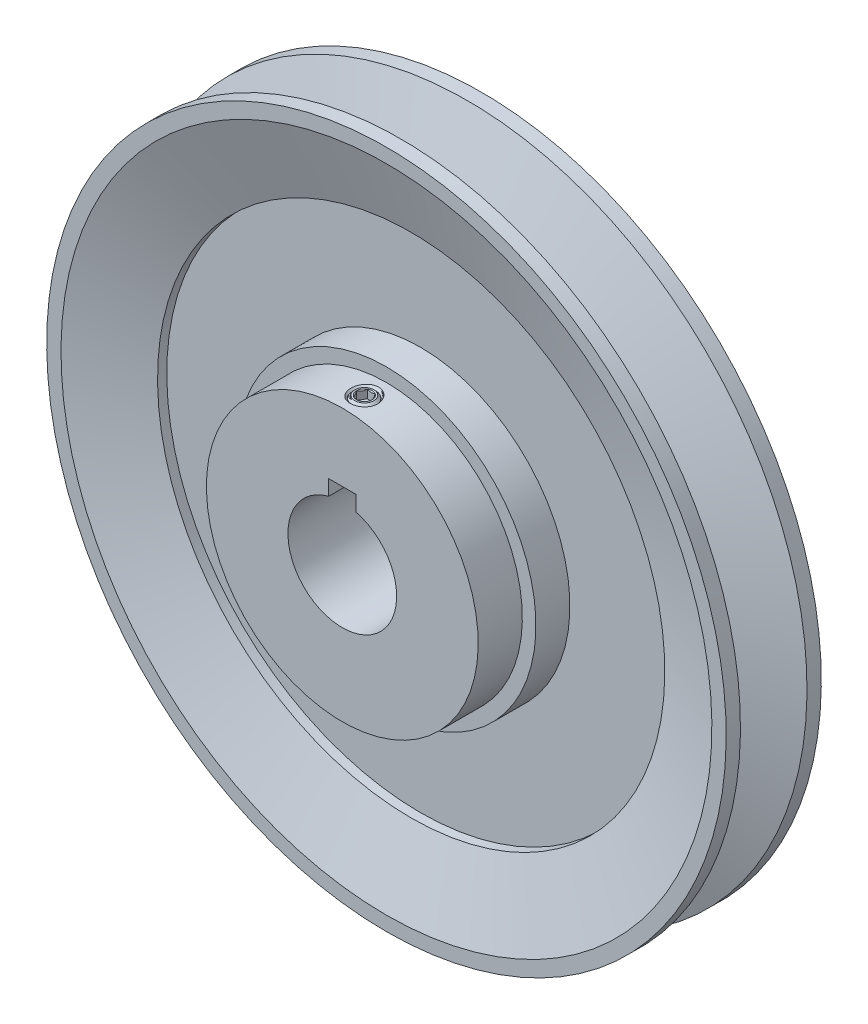
SolidWorks part; units mm, degrees
ref_plane "Front Plane" through (0, 0, 0) normal (0, 0, 1) x (1, 0, 0)
ref_plane "Top Plane" through (0, 0, 0) normal (0, 1, 0) x (1, 0, 0)
ref_plane "Right Plane" through (0, 0, 0) normal (1, 0, 0) x (0, 0, -1)
sketch "Sketch1" plane through (0, 0, 0) normal (1, 0, 0) x (0, 0, -1)
  line L0 (-21.4249, 0) -> (11.1125, 0) construction
  line L1 (-7.7724, 79.375) -> (7.7724, 79.375) construction
  line L2 (7.7724, 79.375) -> (11.1125, 79.375)
  line L5 (-11.1125, 79.375) -> (11.1125, 79.375) construction
  line L7 (-11.1125, 0) -> (-11.1125, 34.925)
  line L9 (-11.1125, 34.925) -> (-3.175, 34.925)
  line L13 (-7.7724, 79.375) -> (-2.3062, 63.5)
  line L14 (-2.3062, 63.5) -> (2.3062, 63.5)
  line L15 (2.3062, 63.5) -> (7.7724, 79.375)
  line L16 (7.9439, 12.7) -> (-21.4249, 12.7) construction
  line L17 (0, 79.375) -> (0, 0) construction
  line L18 (-7.7724, 79.375) -> (-11.1125, 79.375)
  line L20 (-21.4249, 0) -> (-21.4249, 12.7) construction
  line L22 (4.4927, 69.85) -> (-4.4927, 69.85) construction
  line L23 (11.1125, 79.375) -> (11.1125, 0) construction
  line L24 (-3.175, 34.925) -> (-3.175, 59.2544)
  line L26 (-11.1125, 0) -> (7.9439, 0)
  line L27 (-5.3345, 59.2544) -> (-11.1125, 76.0349)
  line L28 (7.9439, 34.925) -> (3.175, 34.925)
  line L29 (3.175, 34.925) -> (3.175, 59.2544)
  line L31 (5.3345, 59.2544) -> (11.1125, 76.0349)
  line L32 (-11.1125, 76.0349) -> (-11.1125, 79.375)
  line L33 (11.1125, 76.0349) -> (11.1125, 79.375)
  line L34 (-21.4249, 31.75) -> (-21.4249, -31.75) construction
  line L35 (6.2419, 74.93) -> (-6.2419, 74.93) construction
  line L36 (-3.175, 59.2544) -> (3.175, 59.2544) construction
  line L37 (-3.175, 34.925) -> (3.175, 34.925) construction
  line L38 (-5.3345, 59.2544) -> (-3.175, 59.2544)
  line L39 (3.175, 59.2544) -> (5.3345, 59.2544)
  line L40 (-2.3062, 63.5) -> (-6.3205, 62.1178) construction
  line L41 (-2.3062, 63.5) -> (-2.3062, 59.2544) construction
  line L42 (7.9439, 34.925) -> (7.9439, 0)
  point P16 (0, 63.5)
  point P33 (0, 59.2544)
  point P34 (0, 34.925)
  point P38 (-11.1061, 0)
  dimension "D1" = 3.175
  dimension "D2" = 6.35
revolve "Revolve1" add sketch "Sketch1" angle 360 about L0
sketch "Sketch2" plane through (0, 0, 0) normal (1, 0, 0) x (0, 0, -1)
  line L0 (11.1125, 0) -> (-21.4249, 0) construction
  line L3 (-11.1061, 0) -> (-11.1061, 31.75)
  line L4 (-11.1061, 31.75) -> (-21.4249, 31.75)
  line L5 (-21.4249, 31.75) -> (-21.4249, 0)
  line L8 (-21.4249, 0) -> (-11.1061, 0)
revolve "Revolve2" add sketch "Sketch2" angle 360 about L0
sketch "Sketch3" plane through (0, 0, 21.4249) normal (0, 0, -1) x (-1, 0, 0)
  line L0 (-3.175, 12.7) -> (3.175, 12.7) construction
  line L1 (-3.175, 15.875) -> (3.175, 15.875) construction
  line L2 (-3.175, 15.875) -> (-3.175, 9.525) construction
  line L3 (-3.175, 9.525) -> (3.175, 9.525) construction
  line L4 (3.175, 15.875) -> (3.175, 9.525) construction
  circle A0 centre (0, 0) radius 12.7
  circle A1 centre (0, 0) radius 69.85 construction
  circle A2 centre (0, 0) radius 74.93 construction
  dimension "Keyway Wd." = 6.35
  dimension "Keyway Dp." = 3.175
extrude "Cut-Extrude1" cut sketch "Sketch3" along normal up to vertex (32.5374 mm away) up to point (0, 0, -11.1125)
sketch "Sketch4" plane through (0, 0, 21.4249) normal (0, 0, -1) x (-1, 0, 0)
  line L0 (-3.175, 15.875) -> (-3.175, 9.525) construction
  line L1 (-3.175, 15.875) -> (3.175, 15.875) construction
  line L2 (3.175, 15.875) -> (3.175, 9.525) construction
  line L3 (-3.175, 9.525) -> (3.175, 9.525) construction
  line L4 (-3.175, 15.875) -> (-3.175, 9.525)
  line L5 (-3.175, 15.875) -> (3.175, 15.875)
  line L6 (3.175, 15.875) -> (3.175, 9.525)
  line L7 (-3.175, 9.525) -> (3.175, 9.525)
  line L8 (-3.175, 12.7) -> (3.175, 12.7) construction
  line L9 (-3.175, 12.7) -> (3.175, 12.7) construction
extrude "Cut-Extrude2" cut sketch "Sketch4" along normal up to vertex (32.5374 mm away) up to point (0, 0, -11.1125)
ref_plane "Plane1" through (0, 31.75, 0) normal (0, 1, 0) x (-1, 0, 0)
sketch "Sketch5" plane through (0, 31.75, 0) normal (0, 1, 0) x (-1, 0, 0)
  line L0 (0, 11.1061) -> (0, 21.4249) construction
  line L7 (0, 19.4405) -> (0, 18.1705) construction
  circle A0 centre (0, 16.2655) radius 3.175 construction
  circle A1 centre (0, 16.2655) radius 2.3813
  dimension "D3" = 0.7937
extrude "Cut-Extrude3" cut sketch "Sketch5" against normal up to vertex (31.75 mm away) up to point (0, 0, 0)
sketch "Sketch6" plane through (0, 31.75, 0) normal (0, 1, 0) x (-1, 0, 0)
  circle A0 centre (0, 16.2655) radius 3.175 construction
  circle A1 centre (0, 16.2655) radius 3.175
  point P3 (0, 19.4405)
curve "Helix/Spiral1" pitch 1.27 height 33.02 turns 26
sketch "Sketch7" plane through (0, 0, 0) normal (1, 0, 0) x (0, 0, -1)
  line L0 (-18.4782, 33.02) -> (-18.4782, 31.75) construction
  line L1 (-18.4782, 31.75) -> (-19.578, 32.385) construction
  line L2 (-19.578, 32.385) -> (-18.4782, 33.02) construction
  line L3 (-18.4782, 31.75) -> (-19.4405, 31.75) construction
  line L4 (-19.4405, 31.75) -> (-19.4405, 32.3056) construction
  line L5 (-19.4405, 32.3056) -> (-19.4405, 32.4644) construction
  line L6 (-18.6156, 31.8294) -> (-18.6156, 32.9406) construction
  line L7 (-19.578, 32.385) -> (-19.4405, 32.385) construction
  line L8 (-18.6156, 32.385) -> (-18.4782, 32.385) construction
  line L9 (-18.5469, 32.9803) -> (-18.5469, 31.7897)
  line L10 (-18.5469, 31.7897) -> (-19.4405, 32.3056)
  line L11 (-19.4405, 32.3056) -> (-19.4405, 32.4644)
  line L12 (-19.4405, 32.4644) -> (-18.5469, 32.9803)
  point P16 (-18.5469, 32.385)
  dimension "D1" = 1.27
  dimension "D2" = 0.1588
sweep "Cut-Sweep1" cut profiles "Sketch7" path "Helix/Spiral1"
sketch "Sketch8" plane through (0, 31.75, 0) normal (0, 1, 0) x (-1, 0, 0)
  circle A0 centre (0, 16.2655) radius 3.3125
extrude "Cut-Extrude4" cut sketch "Sketch8" against normal through all draft 45
sketch "Sketch9" plane through (0, 0, 0) normal (1, 0, 0) x (0, 0, -1)
  line L0 (-16.2655, 31.75) -> (-16.2655, 25.4) construction
  line L1 (-19.4405, 26.3624) -> (-19.4405, 30.7876)
  line L2 (-16.2655, 31.75) -> (-19.4405, 31.75) construction
  line L3 (-16.2655, 31.75) -> (-16.2655, 25.4)
  line L4 (-16.2655, 25.4) -> (-19.4405, 25.4) construction
  line L5 (-19.4405, 31.75) -> (-19.4405, 25.4) construction
  line L6 (-18.4782, 31.75) -> (-19.4405, 30.7876)
  line L7 (-19.4405, 26.3624) -> (-18.4782, 25.4)
  line L8 (-18.4782, 31.75) -> (-16.2655, 31.75)
  line L9 (-18.4782, 25.4) -> (-16.2655, 25.4)
  line L10 (-11.1061, 31.75) -> (-21.4249, 31.75) construction
  line L11 (-18.4782, 31.75) -> (-19.4405, 31.75) construction
  line L12 (-19.4405, 31.75) -> (-19.4405, 30.7876) construction
revolve "Revolve3" add sketch "Sketch9" angle 360 about L0
sketch "Sketch10" plane through (0, 31.75, 0) normal (0, 1, 0) x (-1, 0, 0)
  circle A1 centre (0, 16.2655) radius 3.175
  circle A2 centre (0, 16.2655) radius 3.175
  dimension "D1" = 0
curve "Helix/Spiral2" pitch 1.27 height 7.62 turns 6
sketch "Sketch11" plane through (0, 0, 0) normal (1, 0, 0) x (0, 0, -1)
  line L0 (-19.578, 32.385) -> (-19.578, 31.115) construction
  line L1 (-19.578, 31.115) -> (-18.4782, 31.75) construction
  line L2 (-18.4782, 31.75) -> (-19.578, 32.385) construction
  line L4 (-18.6156, 31.8294) -> (-18.6156, 31.6706)
  line L5 (-18.6156, 31.6706) -> (-19.4405, 31.1944)
  line L6 (-19.4405, 31.1944) -> (-19.4405, 32.3056)
  line L7 (-19.4405, 32.3056) -> (-18.6156, 31.8294)
sweep "Cut-Sweep2" cut profiles "Sketch11" path "Helix/Spiral2"
sketch "Sketch12" plane through (0, 31.75, 0) normal (0, 1, 0) x (1, 0, 0)
  line L1 (1.8331, -16.2655) -> (0.9165, -14.678)
  line L2 (0.9165, -14.678) -> (-0.9165, -14.678)
  line L3 (-0.9165, -14.678) -> (-1.8331, -16.2655)
  line L4 (-1.8331, -16.2655) -> (-0.9165, -17.853)
  line L5 (-0.9165, -17.853) -> (0.9165, -17.853)
  line L6 (0.9165, -17.853) -> (1.8331, -16.2655)
  circle A0 centre (0, -16.2655) radius 1.5875 construction
extrude "Cut-Extrude5" cut sketch "Sketch12" against normal blind 1.9844
sketch "Sketch13" plane through (0, 31.75, 0) normal (0, 1, 0) x (1, 0, 0)
  circle A0 centre (0, -16.2655) radius 1.8331
extrude "Cut-Extrude6" cut sketch "Sketch13" against normal through all draft 45
sketch "Sketch14" [suppressed] plane through (0, 0, -11.1125) normal (0, 0, -1) x (-1, 0, 0)
  line L0 (0, 0) -> (0, 57.9844) construction
  line L1 (0, 0) -> (-50.216, 28.9922) construction
  line L2 (0, 0) -> (50.216, 28.9922) construction
  line L6 (-31.6054, 25.5797) -> (-40.7743, 30.8734)
  line L7 (0, 7.3323) -> (-47.041, 34.4915) construction
  line L8 (31.6054, 25.5797) -> (40.7743, 30.8734)
  line L9 (0, 7.3323) -> (47.041, 34.4915) construction
  circle A1 centre (0, 0) radius 59.2544 construction
  circle A2 centre (0, 0) radius 34.925 construction
  circle A3 centre (0, 0) radius 57.9844 construction
  arc A4 (41.5964, 35.6905) -> (-41.5964, 35.6905) centre (0, 0) ccw
  circle A5 centre (0, 0) radius 34.925 construction
  circle A6 centre (0, 0) radius 54.8094 construction
  arc A7 (-40.7743, 30.8734) -> (-41.5964, 35.6905) centre (-39.1868, 33.623) cw
  arc A8 (41.5964, 35.6905) -> (40.7743, 30.8734) centre (39.1868, 33.623) cw
  arc A9 (27.7088, 26.1502) -> (-27.7088, 26.1502) centre (0, 0) ccw
  arc A10 (-31.6054, 25.5797) -> (-27.7088, 26.1502) centre (-30.0179, 28.3294) ccw
  circle A11 centre (0, 0) radius 38.1 construction
  arc A12 (27.7088, 26.1502) -> (31.6054, 25.5797) centre (30.0179, 28.3294) ccw
  point P10 (43.9493, 0)
  point P18 (31.75, 0)
  dimension "D2" = 6.35
  dimension "D7" = 3.175
  dimension "D4" = 60
  dimension "D1" = 120
  dimension "D5" = 6.35
  dimension "D6" = 3.175
  dimension "D3" = 3.175
extrude "Cut-Extrude7" [suppressed] cut sketch "Sketch14" against normal up to surface (22.225 mm away)
pattern_circular "CirPattern1" [suppressed] count 3 over 360
equation "\"D3@Sketch5\" = \"Set Screw Pitch@Sketch5\" * 5 / 8"
equation "\"D4@Helix/Spiral1\" = \"Set Screw Pitch@Sketch5\""
equation "\"D3@Helix/Spiral1\" = \"D4@Helix/Spiral1\" + ( \"Hub Dia.@Sketch1\" / 2 ) "
equation "\"D1@Sketch7\" = \"D4@Helix/Spiral1\""
equation "\"D2@Sketch7\" = \"D1@Sketch7\" / 8"
equation "\"Set Screw Hex@Sketch12\" = \"Set Screw Dia.@Sketch5\" / 2"
equation "\"D1@Cut-Extrude5\" = \"Set Screw Hex@Sketch12\" * 5 / 8"
equation "\"D4@Helix/Spiral2\" = \"D4@Helix/Spiral1\""
equation "\"D3@Helix/Spiral2\" = \"D4@Helix/Spiral1\" + \"Set Screw Lg.@Sketch9\""
equation "\"D1@Sketch14\" = 360 / \"Spokes@CirPattern1\""
equation "\"D4@Sketch14\" = \"D1@Sketch14\" / 2"
